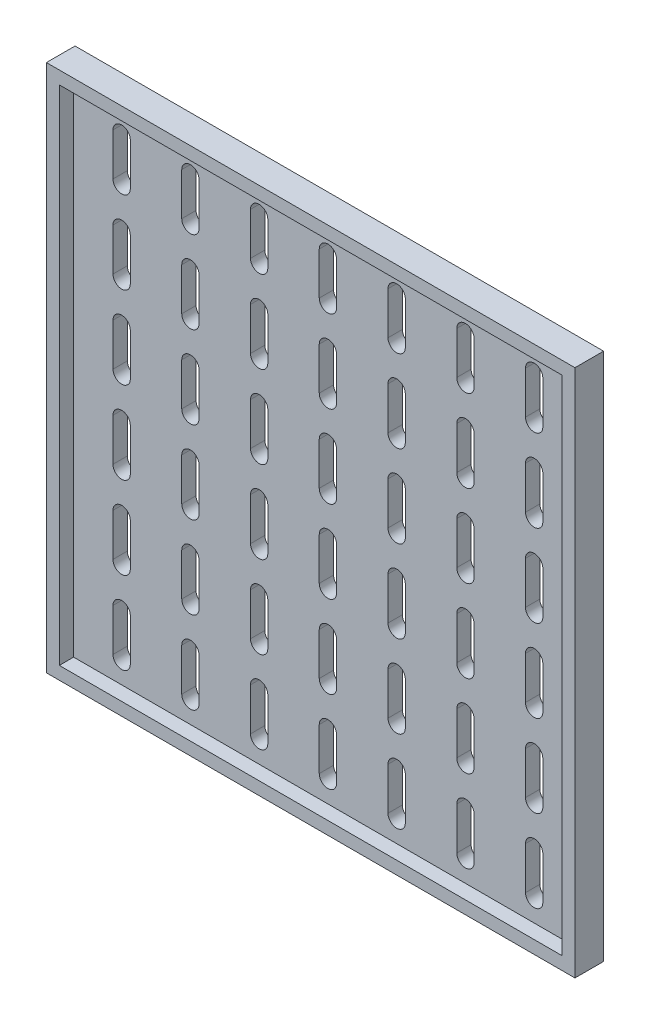
SolidWorks part; units mm, degrees
ref_plane "Front Plane" through (0, 0, 0) normal (0, 0, 1) x (1, 0, 0)
ref_plane "Top Plane" through (0, 0, 0) normal (0, 1, 0) x (1, 0, 0)
ref_plane "Right Plane" through (0, 0, 0) normal (1, 0, 0) x (0, 0, -1)
sketch "Sketch1" plane through (0, 0, 0) normal (0, 0, 1) x (1, 0, 0)
  line L1 (-41.2918, 25.843) -> (32.5082, 25.843)
  line L2 (-41.2918, 25.843) -> (-41.2918, -47.957)
  line L3 (-41.2918, -47.957) -> (32.5082, -47.957)
  line L4 (32.5082, 25.843) -> (32.5082, -47.957)
  line L5 (-39.4918, 24.043) -> (30.7082, 24.043)
  line L6 (-39.4918, 24.043) -> (-39.4918, -46.157)
  line L7 (-39.4918, -46.157) -> (30.7082, -46.157)
  line L8 (30.7082, 24.043) -> (30.7082, -46.157)
  dimension "D1" = 73.8
  dimension "D2" = 73.8
  dimension "D3" = 1.8
  dimension "D4" = 1.8
  dimension "D5" = 1.8
  dimension "D6" = 1.8
extrude "Boss-Extrude1" add sketch "Sketch1" along normal blind 2 contours L2 L3 L4 L1
extrude "Boss-Extrude2" add sketch "Sketch1<3>" along normal blind 4
sketch "Sketch1<3>" plane through (0, 0, 0) normal (0, 0, 1) x (1, 0, 0) same geometry as "Sketch1"
sketch "Sketch2" plane through (0, 0, 0) normal (0, 0, -1) x (-1, 0, 0)
  line L0 (-24.8126, 20.3432) -> (-24.8126, 14.4145) construction
  line L1 (-23.6049, 20.3432) -> (-23.6049, 14.4145)
  line L2 (-26.0203, 20.3432) -> (-26.0203, 14.4145)
  arc A0 (-23.6049, 20.3432) -> (-26.0203, 20.3432) centre (-24.8126, 20.3432) ccw
  arc A1 (-26.0203, 14.4145) -> (-23.6049, 14.4145) centre (-24.8126, 14.4145) ccw
  point P2 (-24.8126, 17.3789)
extrude "Cut-Extrude1" cut sketch "Sketch2" against normal blind 4
pattern_linear "LPattern1" count 7 spacing 9.6 along (-1, 0, 0) count 6 spacing 11.5 along (0, -1, 0) of "Cut-Extrude1"
